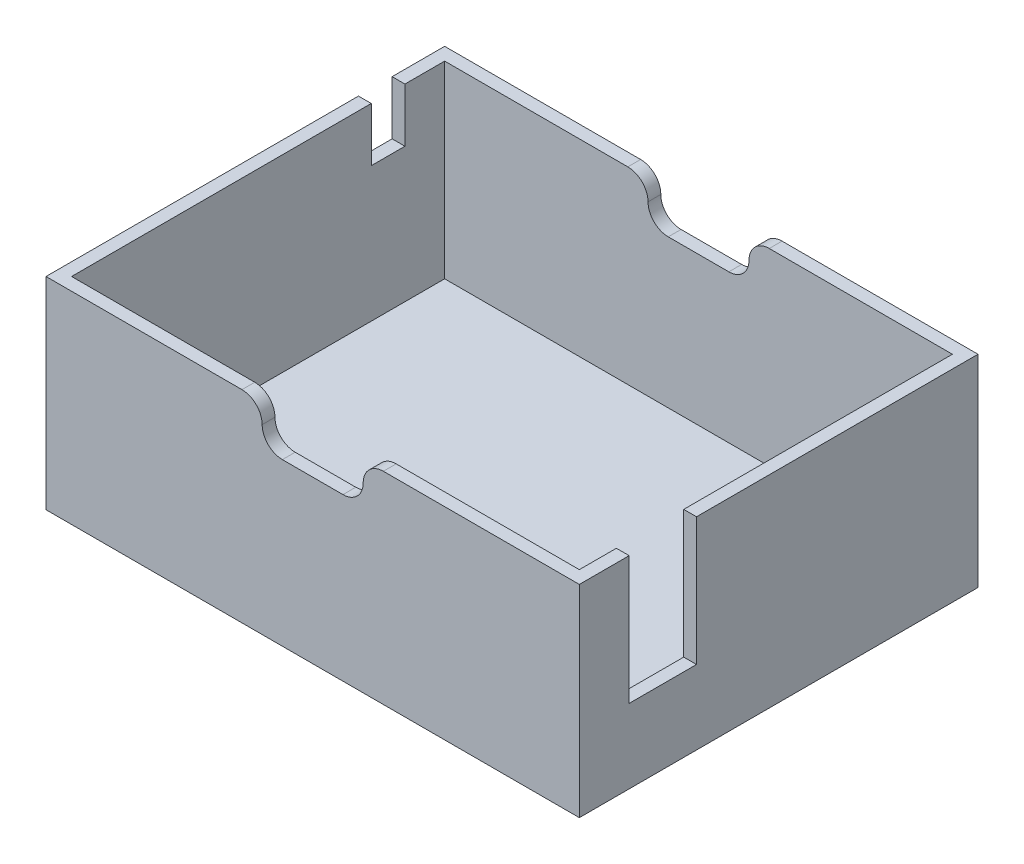
SolidWorks part; units mm, degrees
ref_plane "Front Plane" through (0, 0, 0) normal (0, 0, 1) x (1, 0, 0)
ref_plane "Top Plane" through (0, 0, 0) normal (0, 1, 0) x (1, 0, 0)
ref_plane "Right Plane" through (0, 0, 0) normal (1, 0, 0) x (0, 0, -1)
sketch "Sketch1" plane through (0, 0, 0) normal (0, 1, 0) x (1, 0, 0)
  line L1 (0, 0) -> (100.584, 0)
  line L2 (0, 0) -> (0, 75.184)
  line L3 (0, 75.184) -> (100.584, 75.184)
  line L4 (100.584, 0) -> (100.584, 75.184)
  dimension "D1" = 75.184
  dimension "D2" = 100.584
extrude "Boss-Extrude1" add sketch "Sketch1" along normal blind 2.54
sketch "Sketch2" plane through (0, 2.54, 0) normal (0, 1, 0) x (1, 0, 0)
  line L1 (0, 75.184) -> (100.584, 75.184)
  line L2 (0, 75.184) -> (0, 0)
  line L3 (0, 0) -> (100.584, 0)
  line L4 (100.584, 75.184) -> (100.584, 0)
  line L5 (2.413, 72.771) -> (98.171, 72.771)
  line L6 (2.413, 72.771) -> (2.413, 2.413)
  line L7 (2.413, 2.413) -> (98.171, 2.413)
  line L8 (98.171, 72.771) -> (98.171, 2.413)
  point P10 (0, 37.592)
  point P11 (50.292, 75.184)
  point P12 (50.292, 72.771)
  point P14 (2.413, 37.592)
  dimension "D1" = 70.358
  dimension "D2" = 95.758
extrude "Boss-Extrude2" add sketch "Sketch2" along normal blind 35.56
sketch "Sketch3" plane through (0, 0, -75.184) normal (0, 0, -1) x (-1, 0, 0)
  line L0 (-100.584, 38.1) -> (0, 38.1) construction
  line L1 (-59.817, 38.1) -> (-40.767, 38.1)
  line L2 (-59.817, 38.1) -> (-59.817, 30.48)
  line L3 (-59.817, 30.48) -> (-40.767, 30.48)
  line L4 (-40.767, 38.1) -> (-40.767, 30.48)
  line L5 (-100.584, 0) -> (0, 0) construction
  point P6 (-50.292, 30.48)
  point P7 (-50.292, 0)
  dimension "D1" = 19.05
  dimension "D2" = 7.62
extrude "Cut-Extrude1" cut sketch "Sketch3" against normal through all
fillet "Fillet1" radius 3.81 8 edges at (40.767, 30.48, -1.2065) (59.817, 30.48, -1.2065) (59.817, 30.48, -73.9775) (40.767, 30.48, -73.9775) (40.767, 38.1, -1.2065) (59.817, 38.1, -1.2065) (59.817, 38.1, -73.9775) (40.767, 38.1, -73.9775)
sketch "Sketch4" plane through (0, 0, 0) normal (-1, 0, 0) x (0, 0, 1)
  line L0 (-75.184, 38.1) -> (0, 38.1) construction
  line L1 (-58.928, 38.1) -> (-65.278, 38.1)
  line L2 (-58.928, 31.7503) -> (-58.928, 27.9403)
  line L3 (-58.928, 27.9403) -> (-65.278, 27.9403)
  line L4 (-65.278, 31.7503) -> (-65.278, 27.9403)
  line L6 (-65.278, 31.7503) -> (-65.278, 38.1)
  line L7 (-58.928, 31.7503) -> (-58.928, 38.1)
extrude "Cut-Extrude2" cut sketch "Sketch4" against normal blind 6.35 contours L4 L3 L2 region at (0, 33.0201, -62.103)
sketch "Sketch5" plane through (100.584, 0, 0) normal (1, 0, 0) x (0, 0, -1)
  line L0 (9.398, 19.0503) -> (9.398, 38.1)
  line L1 (22.098, 13.9703) -> (9.398, 13.9703)
  line L2 (22.098, 13.9703) -> (22.098, 19.0503)
  line L4 (9.398, 13.9703) -> (9.398, 19.0503)
  line L5 (0, 38.1) -> (75.184, 38.1) construction
  line L6 (9.398, 38.1) -> (22.098, 38.1)
  line L7 (22.098, 38.1) -> (22.098, 19.0503)
extrude "Cut-Extrude3" cut sketch "Sketch5" against normal blind 6.35
